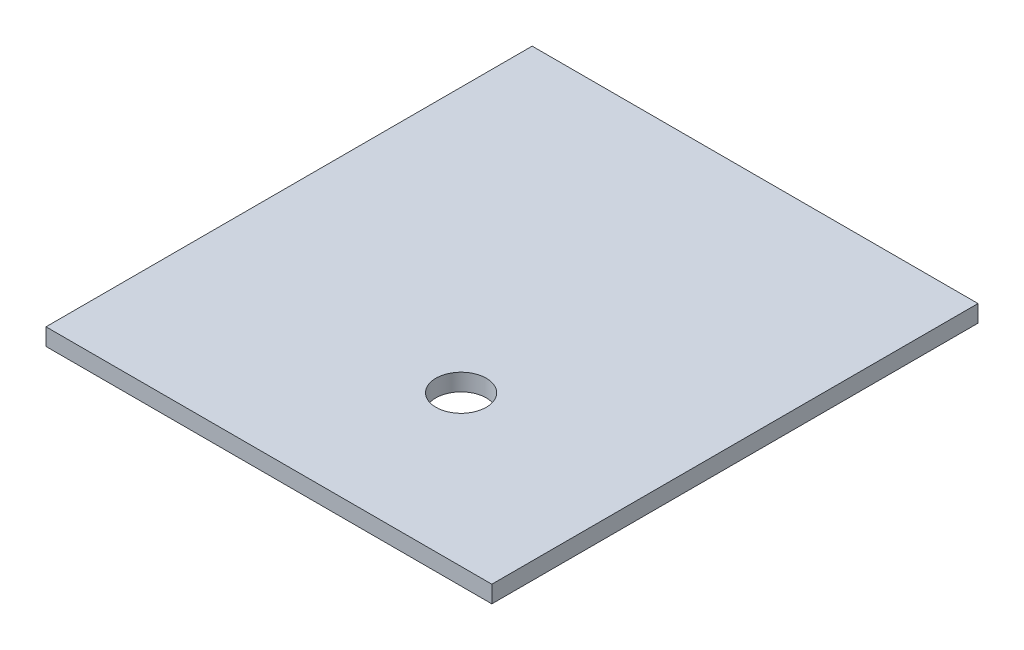
SolidWorks part; units mm, degrees
ref_plane "Front Plane" through (0, 0, 0) normal (0, 0, 1) x (1, 0, 0)
ref_plane "Top Plane" through (0, 0, 0) normal (0, 1, 0) x (1, 0, 0)
ref_plane "Right Plane" through (0, 0, 0) normal (1, 0, 0) x (0, 0, -1)
sketch "Sketch1" plane through (0, 0, 0) normal (0, 1, 0) x (1, 0, 0)
  line L1 (-73.025, -79.629) -> (73.025, -79.629)
  line L2 (-73.025, -79.629) -> (-73.025, 79.629)
  line L3 (-73.025, 79.629) -> (73.025, 79.629)
  line L4 (73.025, -79.629) -> (73.025, 79.629)
  line L5 (-73.025, -79.629) -> (73.025, 79.629) construction
  line L6 (-73.025, 79.629) -> (73.025, -79.629) construction
  point P0 (0, 0)
  dimension "D1" = 146.05
  dimension "D2" = 159.258
extrude "Boss-Extrude1" add sketch "Sketch1" along normal blind 5.588
sketch "Sketch4" plane through (0, 5.588, 0) normal (0, 1, 0) x (1, 0, 0)
  line L0 (-73.025, -79.629) -> (73.025, -79.629) construction
  line L1 (73.025, -79.629) -> (73.025, 79.629) construction
  circle A4 centre (13.6706, -30.353) radius 8.255
  dimension "D1" = 16.51
  dimension "D2" = 49.276
  dimension "D3" = 59.3544
extrude "Cut-Extrude1" cut sketch "Sketch4" against normal up to next
